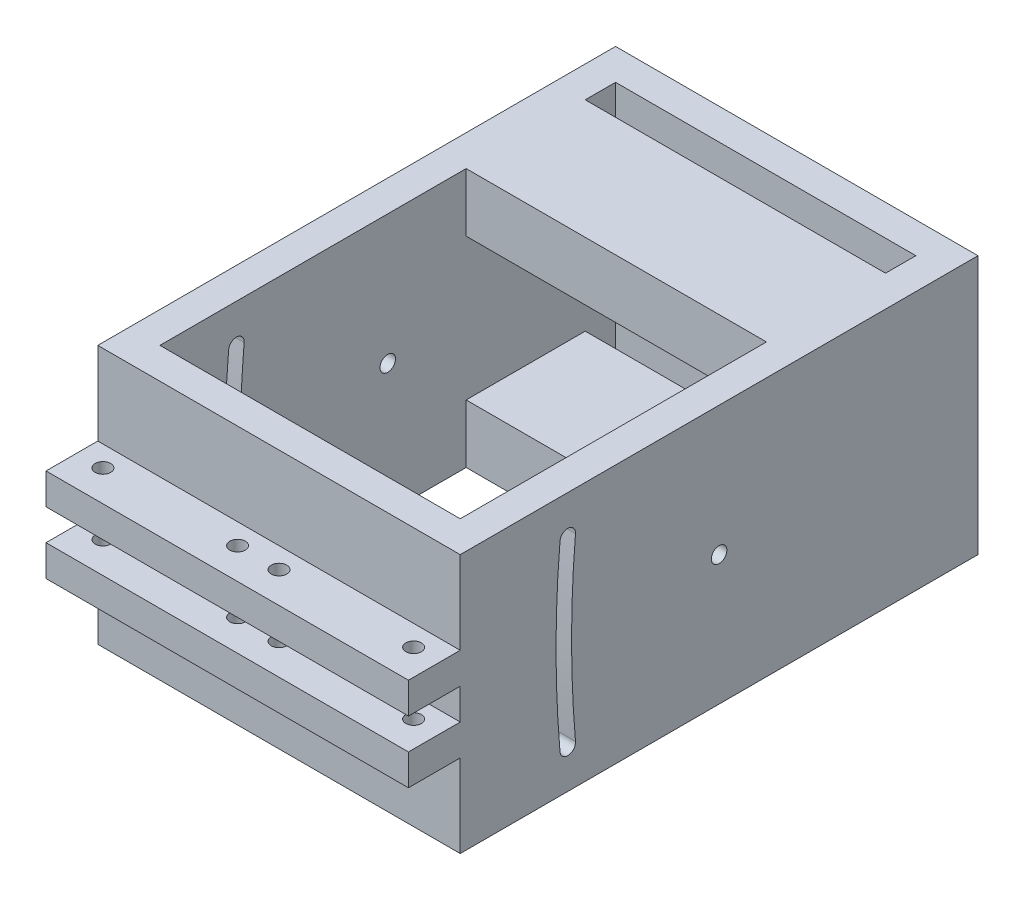
SolidWorks part; units mm, degrees
ref_plane "Front Plane" through (0, 0, 0) normal (0, 0, 1) x (1, 0, 0)
ref_plane "Top Plane" through (0, 0, 0) normal (0, 1, 0) x (1, 0, 0)
ref_plane "Right Plane" through (0, 0, 0) normal (1, 0, 0) x (0, 0, -1)
sketch "Sketch1" plane through (0, 0, 0) normal (0, 1, 0) x (1, 0, 0)
  line L1 (-35, 48.4099) -> (35, 48.4099)
  line L2 (-35, 48.4099) -> (-35, -51.5901)
  line L3 (-35, -51.5901) -> (35, -51.5901)
  line L4 (35, 48.4099) -> (35, -51.5901)
  line L14 (0, -27.5) -> (0, 27.5) construction
  line L16 (-29, 42.4099) -> (29, 42.4099)
  line L17 (-29, 42.4099) -> (-29, -45.5901)
  line L18 (-29, -45.5901) -> (29, -45.5901)
  line L19 (29, 42.4099) -> (29, -45.5901)
  point P14 (0, -51.5901)
  dimension "D1" = 70
  dimension "D2" = 100
  dimension "D3" = 6
  dimension "D4" = 6
  dimension "D5" = 6
  dimension "D6" = 6
  dimension "D9" = 0
extrude "main_body" add sketch "Sketch1" along normal blind 50
sketch "Sketch2" plane through (35, 0, 0) normal (1, 0, 0) x (0, 0, -1)
  line L0 (-51.5901, 50) -> (-51.5901, 0) construction
  circle A0 centre (-1.5901, 25) radius 1.5
  point P4 (-51.5901, 25)
  dimension "D1" = 3
  dimension "D2" = 0
  dimension "D3" = 50
sketch "Sketch3" plane through (0, 0, 51.5901) normal (0, 0, 1) x (1, 0, 0)
  line L0 (-35, 50) -> (35, 50) construction
  line L1 (35, 50) -> (35, 0) construction
  circle A0 centre (0, 25) radius 1.5
  point P4 (0, 50)
  point P7 (35, 25)
  dimension "D1" = 0
  dimension "D3" = 3
  dimension "D2" = 0
extrude "back_wire_hole" cut sketch "Sketch3" against normal up to next
sketch "Sketch6" plane through (0, 0, -48.4099) normal (0, 0, -1) x (-1, 0, 0)
  line L0 (35, 50) -> (35, 0) construction
  line L1 (-35, 50) -> (35, 50) construction
  circle A0 centre (0, 25) radius 1.5
  point P4 (35, 25)
  point P7 (0, 50)
  dimension "D1" = 0
  dimension "D3" = 3
  dimension "D2" = 0
extrude "front_wire_hole" cut sketch "Sketch6" against normal up to next
sketch "Sketch4" plane through (0, 0, 51.5901) normal (0, 0, 1) x (1, 0, 0)
  line L6 (-35, 50) -> (-35, 0) construction
  line L8 (-35, 34) -> (35, 34)
  line L10 (-35, 34) -> (-35, 28)
  line L12 (-35, 28) -> (35, 28)
  line L13 (35, 34) -> (35, 28)
  line L14 (35, 50) -> (35, 0) construction
  point P8 (-35, 25)
  dimension "D1" = 6
  dimension "D2" = 3
extrude "back_lip" add sketch "Sketch4" along normal blind 10
ref_plane "central_horizontal_plane" [suppressed] through (0, 25, 0) normal (0, 1, 0) x (1, 0, 0)
mirror "back_lip_mirror" about plane through (0, 25, 0) normal (0, 1, 0) of "back_lip"
sketch "Sketch5" plane through (0, 34, 0) normal (0, 1, 0) x (1, 0, 0)
  line L0 (35, -61.5901) -> (-35, -61.5901) construction
  line L1 (35, -51.5901) -> (-35, -51.5901) construction
  line L2 (35, -61.5901) -> (35, -51.5901) construction
  line L3 (0, -61.5901) -> (0, -51.5901) construction
  circle A0 centre (4, -55.5901) radius 1.5
  circle A1 centre (30, -55.5901) radius 1.5
  circle A2 centre (-30, -55.5901) radius 1.5
  circle A3 centre (-4, -55.5901) radius 1.5
  point P4 (0, -61.5901)
  dimension "D1" = 4
  dimension "D3" = 0
  dimension "D5" = 3
  dimension "D6" = 3
  dimension "D2" = 4
  dimension "D4" = 5
extrude "back_lip_holes" cut sketch "Sketch5" against normal through all
extrude "geared_arm_hole" cut sketch "Sketch2" against normal up to next
mirror "geared_arm_hole_mirror" about plane through (0, 0, 0) normal (1, 0, 0) of "geared_arm_hole"
sketch "alignment_sketch" plane through (35, 0, 0) normal (1, 0, 0) x (0, 0, -1)
  line L0 (-1.5901, 25) -> (48.4099, 25) construction
  line L1 (48.4099, 50) -> (48.4099, 0) construction
  line L2 (-1.5901, 25) -> (19.553, 32.6955) construction
  line L3 (-1.5901, 25) -> (19.553, 17.3045) construction
  point P5 (19.553, 32.6955)
  point P6 (0, 0)
  point P8 (19.553, 17.3045)
  point P10 (0, 0)
  dimension "D2" = 22.5
  dimension "D1" = 20
ref_axis "top_servo_alignment_axis" through (-55.368, 32.6955, -19.553) along (1, 0, 0)
ref_axis "bottom_servo_alignment_axis" through (-54.8199, 17.3045, -19.553) along (1, 0, 0)
sketch "Sketch10" plane through (-29, 0, 0) normal (1, 0, 0) x (0, 0, -1)
  line L0 (-51.5901, 0) -> (48.4099, 0) construction
  line L1 (13.553, 0) -> (36.553, 0)
  line L2 (13.553, 0) -> (13.553, 11.3045)
  line L3 (13.553, 11.3045) -> (36.553, 11.3045)
  line L4 (36.553, 0) -> (36.553, 11.3045)
  line L5 (48.4099, 25) -> (47.0508, 25) construction
  line L6 (-1.5901, 25) -> (48.4099, 25) construction
  line L7 (13.553, 38.6955) -> (36.553, 38.6955)
  line L8 (36.553, 50) -> (36.553, 38.6955)
  line L9 (13.553, 50) -> (36.553, 50)
  line L10 (13.553, 50) -> (13.553, 38.6955)
  dimension "D1" = 6
  dimension "D2" = 23
  dimension "D3" = 6
extrude "servo_mount_main_extrusion" add sketch "Sketch10" along normal up to surface (58 mm away) up to face at (29, 25, 3.0901)
sketch "Sketch11" plane through (35, 0, 0) normal (1, 0, 0) x (0, 0, -1)
  arc A0 (-30.823, 7.5) -> (-30.823, 42.5) centre (168.4099, 25) cw construction
  arc A1 (-32.3172, 42.6313) -> (-32.3172, 7.3687) centre (168.4099, 25) ccw
  arc A2 (-29.3287, 42.3688) -> (-29.3287, 7.6312) centre (168.4099, 25) ccw
  arc A3 (-29.3287, 42.3688) -> (-32.3172, 42.6313) centre (-30.823, 42.5) ccw
  arc A4 (-32.3172, 7.3687) -> (-29.3287, 7.6312) centre (-30.823, 7.5) ccw
  point P3 (-31.5901, 25)
  dimension "D1" = 1.5
  dimension "D2" = 200
  dimension "D3" = 35
  dimension "D4" = 170
extrude "wing_connection_slot" cut sketch "Sketch11" against normal up to next
mirror "wing_connection_slot_mirror" about plane through (0, 0, 0) normal (1, 0, 0) of "wing_connection_slot"
equation "\"gear_spacing\"= 22.5mm"
equation "\"D2@alignment_sketch\" = \"gear_spacing\""
equation "\"gear_angle_offset\"= 20deg"
equation "\"D1@alignment_sketch\" = \"gear_angle_offset\""
